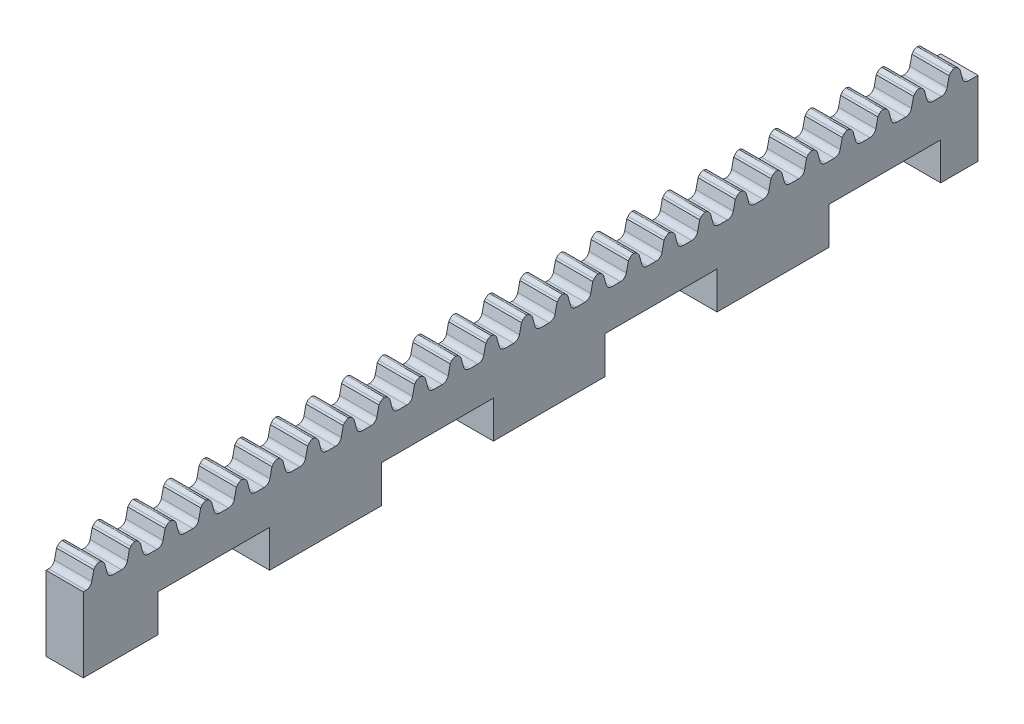
SolidWorks part; units mm, degrees
ref_plane "Front Plane" through (0, 0, 0) normal (0, 0, 1) x (1, 0, 0)
ref_plane "Top Plane" through (0, 0, 0) normal (0, 1, 0) x (1, 0, 0)
ref_plane "Right Plane" through (0, 0, 0) normal (1, 0, 0) x (0, 0, -1)
sketch "Sketch2" plane through (0, 0, 0) normal (0, 0, 1) x (1, 0, 0)
  line L1 (3.175, -3.175) -> (-3.175, -3.175)
  line L2 (3.175, -3.175) -> (3.175, 3.175)
  line L3 (3.175, 3.175) -> (-3.175, 3.175)
  line L4 (-3.175, -3.175) -> (-3.175, 3.175)
  line L5 (3.175, -3.175) -> (-3.175, 3.175) construction
  line L6 (3.175, 3.175) -> (-3.175, -3.175) construction
  point P0 (0, 0)
  dimension "D1" = 6.35
  dimension "D2" = 6.35
extrude "Boss-Extrude1" add sketch "Sketch2" along normal mid plane 152.4
sketch "Sketch3" plane through (3.175, 0, 0) normal (1, 0, 0) x (0, 0, -1)
  line L0 (-74.93, 3.175) -> (-74.4069, 5.5607)
  line L1 (-76.2, 3.175) -> (76.2, 3.175) construction
  line L3 (-72.5613, 5.5344) -> (-71.93, 3.175)
  line L4 (-76.2, -3.175) -> (-76.2, 3.175) construction
  line L5 (-71.93, 3.175) -> (-74.93, 3.175)
  line L6 (-74.4069, 5.5607) -> (-73.8895, 6.223)
  line L7 (-73.8895, 6.223) -> (-73.0432, 6.223)
  line L9 (-73.0432, 6.223) -> (-72.5613, 5.5344)
  point P8 (0, 0)
  dimension "D1" = 1.27
  dimension "D2" = 52
  dimension "D3" = 3
  dimension "D4" = 3.048
  dimension "D5" = 20
extrude "Boss-Extrude2" add sketch "Sketch3" against normal up to surface (6.35 mm away) up to face at (-3.175, 0, 0)
fillet "Fillet2" radius 1.016 2 edges at (0, 6.223, 73.8895) (0, 6.223, 73.0432)
fillet "Fillet1" radius 1.016 2 edges at (0, 3.175, 71.93) (0, 3.175, 74.93)
pattern_linear "LPattern1" count 25 spacing 6.0706 along (0, 0, -1) of "Boss-Extrude2", "Fillet1", "Fillet2"
sketch "Sketch4" plane through (3.175, 0, 0) normal (1, 0, 0) x (0, 0, -1)
  line L0 (76.2, -3.175) -> (76.2, 3.175) construction
  line L1 (-76.2, -3.175) -> (76.2, -3.175)
  line L2 (-76.2, -3.175) -> (-76.2, -9.525)
  line L3 (-76.2, -9.525) -> (76.2, -9.525)
  line L4 (76.2, -3.175) -> (76.2, -9.525)
  dimension "D1" = 6.35
extrude "Boss-Extrude3" add sketch "Sketch4" against normal up to surface (6.35 mm away) up to face at (-3.175, 4.6946, 0.6032)
sketch "Sketch5" plane through (3.175, 0, 0) normal (1, 0, 0) x (0, 0, -1)
  line L0 (-76.2, -9.525) -> (76.2, -9.525) construction
  line L1 (69.85, -9.525) -> (50.8, -9.525)
  line L2 (69.85, -9.525) -> (69.85, -3.175)
  line L3 (69.85, -3.175) -> (50.8, -3.175)
  line L4 (50.8, -9.525) -> (50.8, -3.175)
  line L5 (76.2, -9.525) -> (76.2, 3.175) construction
  dimension "D1" = 6.35
  dimension "D2" = 19.05
  dimension "D3" = 6.35
extrude "Cut-Extrude1" cut sketch "Sketch5" against normal through all
pattern_linear "LPattern2" count 4 spacing 38.1 along (0, 0, 1) of "Cut-Extrude1"
